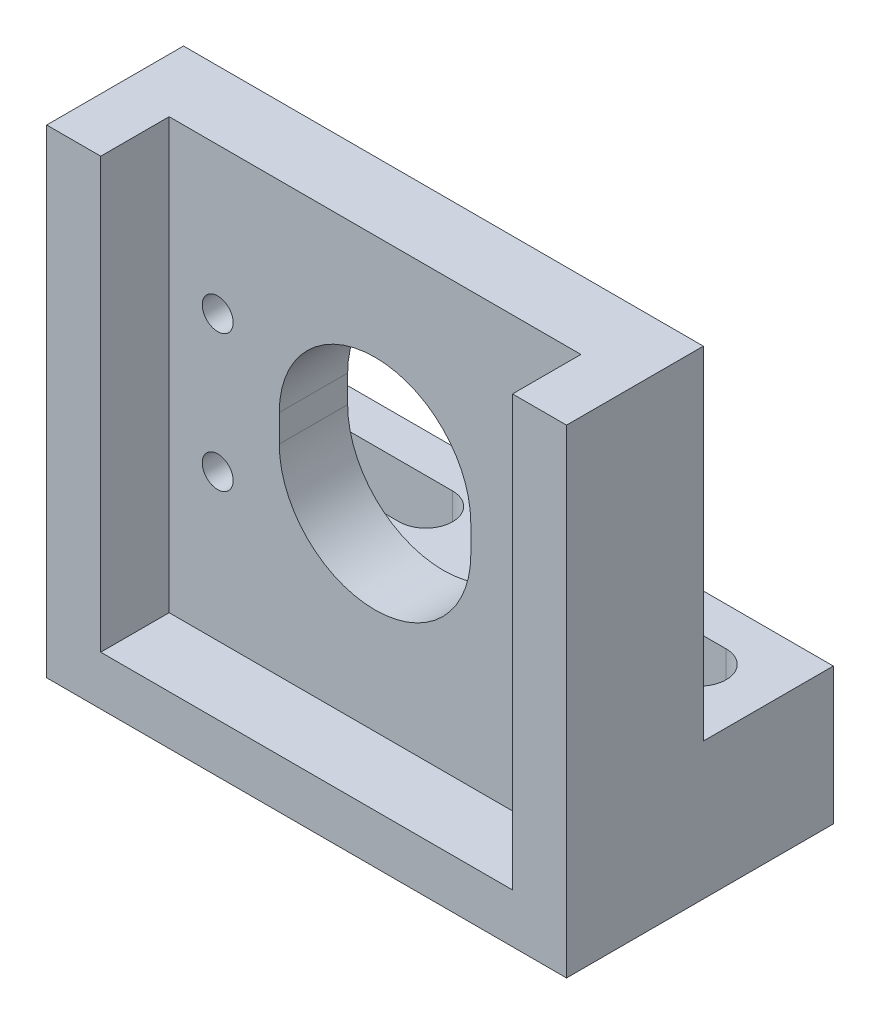
SolidWorks part; units mm, degrees
material "6063-T5"
ref_plane "Front Plane" through (0, 0, 0) normal (0, 0, 1) x (1, 0, 0)
ref_plane "Top Plane" through (0, 0, 0) normal (0, 1, 0) x (1, 0, 0)
ref_plane "Right Plane" through (0, 0, 0) normal (1, 0, 0) x (0, 0, -1)
sketch "Sketch1" plane through (0, 0, 0) normal (0, 1, 0) x (1, 0, 0)
  line L1 (-26.2238, 44.0559) -> (11.7762, 44.0559)
  line L2 (-26.2238, 44.0559) -> (-26.2238, 24.5559)
  line L3 (-26.2238, 24.5559) -> (11.7762, 24.5559)
  line L4 (11.7762, 44.0559) -> (11.7762, 24.5559)
  dimension "D1" = 38
  dimension "D2" = 19.5
extrude "Boss-Extrude1" add sketch "Sketch1" along normal blind 35 contours L1 L4 L3 L2
sketch "Sketch2" plane through (0, 35, 0) normal (0, 1, 0) x (1, 0, 0)
  line L0 (11.7762, 44.0559) -> (11.7762, 24.5559) construction
  line L1 (-26.2238, 44.0559) -> (11.7762, 44.0559)
  line L2 (-26.2238, 44.0559) -> (-26.2238, 34.5559)
  line L3 (-26.2238, 34.5559) -> (11.7762, 34.5559)
  line L4 (11.7762, 44.0559) -> (11.7762, 34.5559)
  line L5 (-26.2238, 24.5559) -> (11.7762, 24.5559) construction
  dimension "D1" = 10
extrude "Cut-Extrude1" cut sketch "Sketch2" against normal offset from surface (25 mm away) 10 up to face at (-7.2238, 0, -34.3059)
sketch "Sketch4" plane through (0, 10, 0) normal (0, 1, 0) x (1, 0, 0)
  line L0 (6.7762, 39.271) -> (-1.2238, 39.271) construction
  line L1 (6.7762, 37.316) -> (-1.2238, 37.316)
  line L2 (6.7762, 41.226) -> (-1.2238, 41.226)
  line L3 (-7.2238, 34.5559) -> (-7.2238, 44.0559)
  line L4 (11.7762, 34.5559) -> (-26.2238, 34.5559) construction
  line L5 (-26.2238, 44.0559) -> (11.7762, 44.0559) construction
  line L6 (-21.2238, 39.271) -> (-13.2238, 39.271) construction
  line L7 (-21.2238, 37.316) -> (-13.2238, 37.316)
  line L8 (-21.2238, 41.226) -> (-13.2238, 41.226)
  line L9 (-26.2238, 34.5559) -> (-26.2238, 44.0559) construction
  arc A0 (6.7762, 37.316) -> (6.7762, 41.226) centre (6.7762, 39.271) ccw
  arc A1 (-1.2238, 41.226) -> (-1.2238, 37.316) centre (-1.2238, 39.271) ccw
  arc A2 (-21.2238, 37.316) -> (-21.2238, 41.226) centre (-21.2238, 39.271) cw
  arc A3 (-13.2238, 41.226) -> (-13.2238, 37.316) centre (-13.2238, 39.271) cw
  point P2 (2.7762, 39.271)
  point P15 (-17.2238, 39.271)
  dimension "D2" = 1.955
  dimension "D1" = 8
  dimension "D3" = 5
  dimension "D4" = 20
extrude "6-32 slot" cut sketch "Sketch4" against normal up to next contours A3 L8 A2 L7 | L2 A1 L1 A0 region at (2.7762, 10, -39.271) region at (-17.2238, 10, -39.271)
sketch "Sketch5" plane through (0, 0, -24.5559) normal (0, 0, 1) x (1, 0, 0)
  line L0 (-7.2238, 35) -> (-7.2238, 0)
  line L1 (-26.2238, 35) -> (11.7762, 35) construction
  line L2 (-26.2238, 0) -> (11.7762, 0) construction
  line L3 (-7.2238, 18.3) -> (-7.2238, 20.3) construction
  line L4 (-22.2738, 3.6) -> (7.8262, 3.6)
  line L5 (-22.2738, 3.6) -> (-22.2738, 35)
  line L6 (-22.2738, 35) -> (7.8262, 35)
  line L7 (7.8262, 3.6) -> (7.8262, 35)
  line L8 (-22.2738, 3.6) -> (7.8262, 35) construction
  line L9 (-22.2738, 35) -> (7.8262, 3.6) construction
  line L10 (-14.2238, 18.3) -> (-14.2238, 20.3)
  line L11 (-0.2238, 18.3) -> (-0.2238, 20.3)
  line L16 (7.8262, 19.3) -> (-22.2738, 19.3)
  arc A1 (-14.2238, 18.3) -> (-0.2238, 18.3) centre (-7.2238, 18.3) ccw
  arc A2 (-0.2238, 20.3) -> (-14.2238, 20.3) centre (-7.2238, 20.3) ccw
  circle A3 centre (-18.7238, 24.3) radius 1.13
  circle A4 centre (4.2762, 24.3) radius 1.13
  circle A5 centre (4.2762, 14.3) radius 1.13
  circle A6 centre (-18.7238, 14.3) radius 1.13
  point P6 (-7.2238, 19.3)
  point P13 (-7.2238, 19.3)
  point P19 (-7.2238, 33.75)
  line M8 (11.7762, 35) -> (-26.2238, 35)
  dimension "D4" = 7
  dimension "D6" = 2.26
  dimension "D1" = 30.1
  dimension "D2" = 19.3
  dimension "D3" = 0
  dimension "D5" = 2
  dimension "D7" = 23
  dimension "D8" = 10
  dimension "D9" = 0
extrude "aperture thru hole" cut sketch "Sketch5" against normal up to next contours L0 A2 L10 A1 | L11 A2 L0 A1 | L11 A2 L10 A1 region at (-10.2761, 22.7367, -24.5559) region at (-4.1715, 15.8633, -24.5559)
extrude "Cut-Extrude5" cut sketch "Sketch5<4>" against normal offset from surface (5 mm away) 5 contours A2 L0 L5 L16 L10 A3 M8 | A2 L11 L16 L7 L0 A4 M8 | A1 L0 L4 L7 L16 L11 A5 | A1 L10 L16 L5 L4 L0 A6 region at (1.305, 28.2859, -24.5559) region at (-15.7525, 28.2859, -24.5559) region at (-15.7525, 10.3141, -24.5559) region at (1.305, 10.3141, -24.5559) up to face at (-7.2238, 19.3, -34.5559)
sketch "Sketch5<4>" plane through (0, 0, -24.5559) normal (0, 0, 1) x (1, 0, 0) same geometry as "Sketch5"
hole_wizard "#4-40 Tapped Hole1" positions "Sketch6" profile "Sketch7" tap size "#4-40" standard "ANSI Inch" end condition through all
sketch "Sketch6" plane through (0, 0, -24.5559) normal (0, 0, 1) x (1, 0, 0)
  point P0 (-18.7238, 24.3)
  point P3 (-18.7238, 14.3)
  point P6 (4.2762, 14.3)
  point P9 (4.2762, 24.3)
sketch "Sketch7" plane through (-18.7238, 24.3, -24.5559) normal (1, 0, 0) x (0, -1, 0)
  line L0 (0, 0) -> (0, 19.5)
  line L1 (0, 19.5) -> (1.1303, 19.5)
  line L2 (1.1303, 19.5) -> (1.1303, 0)
  line L5 (1.1303, 0) -> (0, 0)
  line L11 (0, -6.35) -> (0, 107.95) construction
  dimension "Thru Tap Drill Dia." = 2.2606
  dimension "Thru Tap Drill Depth" = 19.5
cosmetic thread "Hole Thread1" parameters "D2"=2.8448
cosmetic thread "Hole Thread2" parameters "D2"=2.8448
cosmetic thread "Hole Thread3" parameters "D2"=2.8448
cosmetic thread "Hole Thread4" parameters "D2"=2.8448
